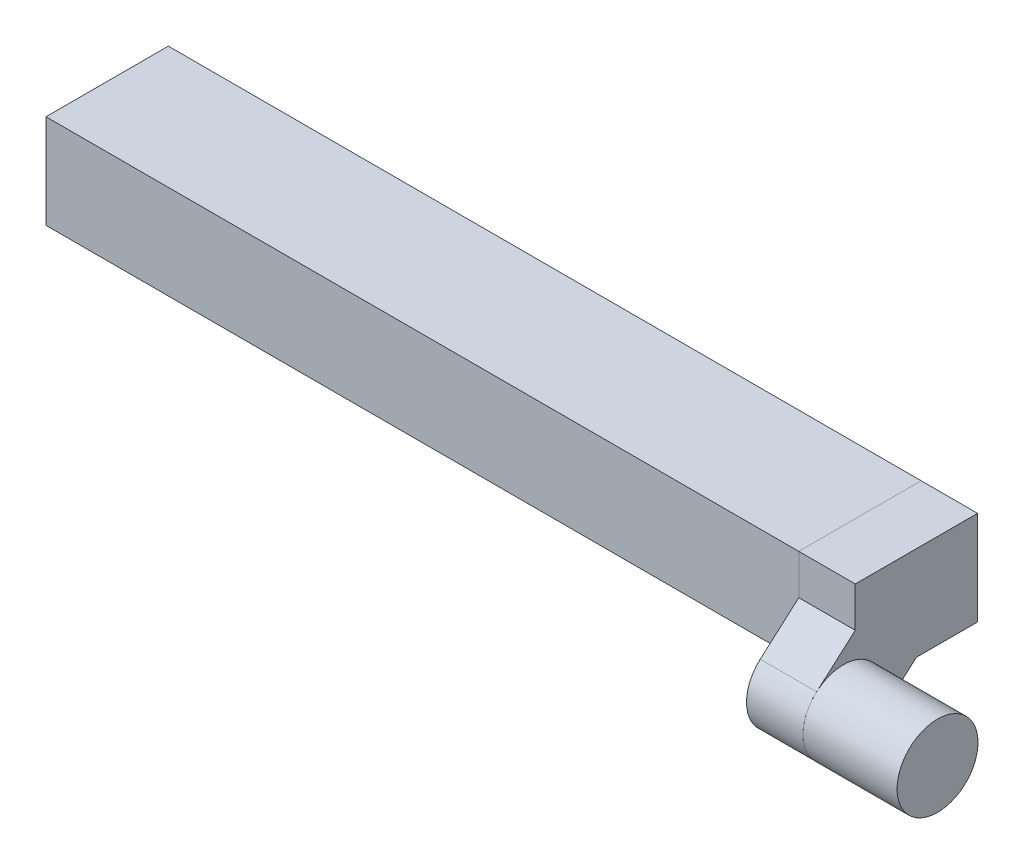
SolidWorks part; units mm, degrees
ref_plane "Front Plane" through (0, 0, 0) normal (0, 0, 1) x (1, 0, 0)
ref_plane "Top Plane" through (0, 0, 0) normal (0, 1, 0) x (1, 0, 0)
ref_plane "Right Plane" through (0, 0, 0) normal (1, 0, 0) x (0, 0, -1)
sketch "Sketch2" plane through (0, 0, 0) normal (1, 0, 0) x (0, 0, -1)
  line L1 (-2.05, -2.05) -> (2.05, -2.05)
  line L2 (-2.05, -2.05) -> (-2.05, 2.05)
  line L3 (-2.05, 2.05) -> (2.05, 2.05)
  line L4 (2.05, -2.05) -> (2.05, 2.05)
  line L5 (-2.05, -2.05) -> (2.05, 2.05) construction
  line L6 (-2.05, 2.05) -> (2.05, -2.05) construction
  line L7 (3.25, -2.5) -> (-3.25, -2.5)
  line L8 (3.25, -2.5) -> (3.25, 2.5)
  line L9 (3.25, 2.5) -> (-3.25, 2.5)
  line L10 (-3.25, -2.5) -> (-3.25, 2.5)
  line L11 (3.25, -2.5) -> (-3.25, 2.5) construction
  line L12 (3.25, 2.5) -> (-3.25, -2.5) construction
  point P0 (0, 0)
  point P5 (0, 0)
  dimension "D1" = 4.1
  dimension "D2" = 4.1
  dimension "D3" = 6.5
  dimension "D4" = 5
extrude "Boss-Extrude1" add sketch "Sketch2" along normal blind 10
extrude "Boss-Extrude2" add sketch "Sketch2<2>" along normal blind 25 from offset 15 contours L1 L4 L3 L2 | L10 L7 L8 L9 L4 L1 L2 L3 region at (0, 0, 0) region at (0, -2.418, 0)
sketch "Sketch2<2>" plane through (0, 0, 0) normal (1, 0, 0) x (0, 0, -1) same geometry as "Sketch2"
sketch "Sketch5" plane through (40, 0, 0) normal (1, 0, 0) x (0, 0, -1)
  line L6 (-3.25, 2.5) -> (3.25, 2.5)
  line L7 (3.25, 2.5) -> (3.25, -2.5)
  line L8 (3.25, -2.5) -> (0, -2.5)
  line L9 (-3.25, -2.5) -> (3.25, -2.5) construction
  line L10 (0, -2.5) -> (-2.4563, -4.664)
  line L11 (-5.2988, -1.4375) -> (-3.25, 0.3675)
  line L12 (-3.25, -2.5) -> (-3.25, 2.5) construction
  line L13 (-5.2988, -1.4375) -> (-2.4563, -4.664) construction
  line L14 (-3.25, 0.3675) -> (-3.25, 2.5)
  arc A1 (-5.2988, -1.4375) -> (-2.4563, -4.664) centre (-3.8775, -3.0507) ccw
  dimension "D3" = 5
  dimension "D4" = 4.3
extrude "Boss-Extrude3" add sketch "Sketch5" along normal blind 3
sketch "Sketch6" plane through (43, 0, 0) normal (1, 0, 0) x (0, 0, -1)
  circle A1 centre (-3.8775, -3.0507) radius 2.15
  dimension "D1" = 4.3
extrude "Boss-Extrude4" add sketch "Sketch6" along normal blind 5
extrude "Boss-Extrude5" add sketch "Sketch2<4>" along normal blind 5 from offset 10
sketch "Sketch2<4>" plane through (0, 0, 0) normal (1, 0, 0) x (0, 0, -1) same geometry as "Sketch2"
